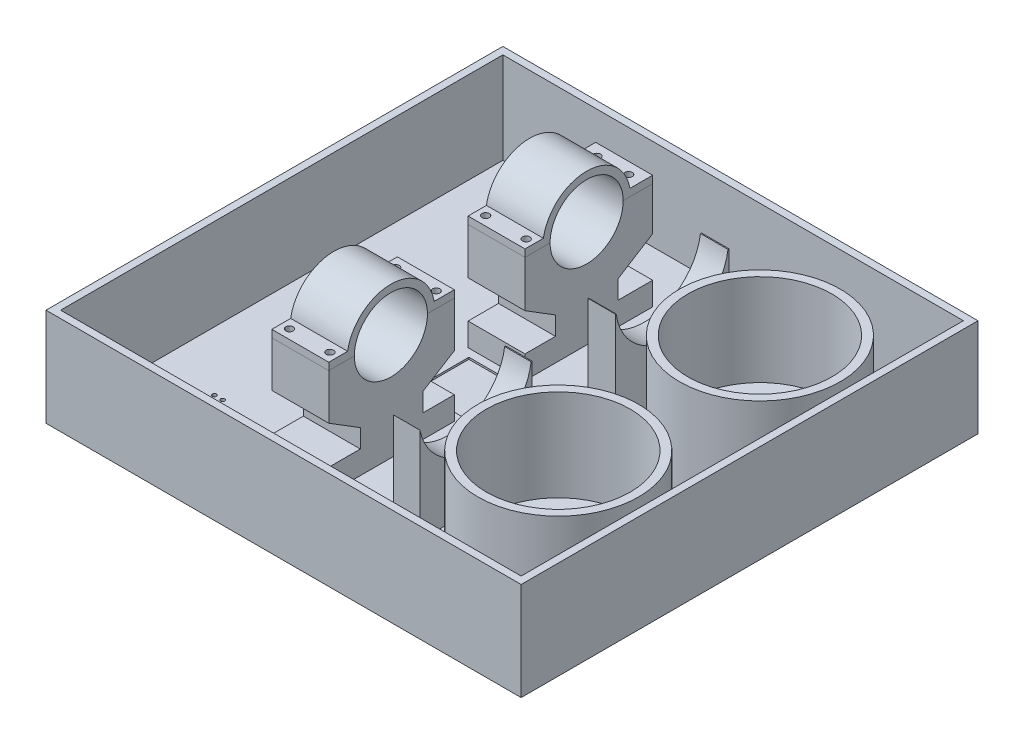
SolidWorks part; units mm, degrees
ref_plane "Front Plane" through (0, 0, 0) normal (0, 0, 1) x (1, 0, 0)
ref_plane "Top Plane" through (0, 0, 0) normal (0, 1, 0) x (1, 0, 0)
ref_plane "Right Plane" through (0, 0, 0) normal (1, 0, 0) x (0, 0, -1)
ref_plane "Plane1" through (0, -430, 0) normal (0, 1, 0) x (1, 0, 0)
sketch "Sketch2" plane through (0, -430, 0) normal (0, 1, 0) x (1, 0, 0)
  line L1 (-595.6003, 318.2592) -> (704.3997, 318.2592)
  line L2 (-595.6003, 318.2592) -> (-595.6003, -931.7408)
  line L3 (-595.6003, -931.7408) -> (704.3997, -931.7408)
  line L4 (704.3997, 318.2592) -> (704.3997, -931.7408)
  dimension "D1" = 1250
  dimension "D2" = 1300
extrude "Boss-Extrude1" add sketch "Sketch2" along normal blind 8 and the other way blind 10
sketch "Sketch3" plane through (0, -422, 0) normal (0, 1, 0) x (1, 0, 0)
  line L0 (-595.6003, -306.7408) -> (-355.8239, -306.7408) construction
  line L1 (-179.3433, 155.9673) -> (-23.5146, 155.9673)
  line L2 (-179.3433, 155.9673) -> (-179.3433, -193.2391)
  line L3 (-179.3433, -193.2391) -> (-23.5146, -193.2391)
  line L4 (-23.5146, 155.9673) -> (-23.5146, -193.2391)
  line L5 (-595.6003, 318.2592) -> (-595.6003, -931.7408) construction
  line L7 (-179.3433, -386.6168) -> (-23.5146, -386.6168)
  line L8 (-179.3433, -386.6168) -> (-179.3433, -730.1907)
  line L9 (-179.3433, -730.1907) -> (-23.5146, -730.1907)
  line L10 (-23.5146, -386.6168) -> (-23.5146, -730.1907)
extrude "Boss-Extrude2" add sketch "Sketch3" along normal blind 500 contours L10 L7 L8 L9 | L4 L1 L2 L3 region at (-101.429, -422, 18.6359) region at (-101.429, -422, 558.4038)
sketch "Sketch5" plane through (-23.5146, 0, 0) normal (1, 0, 0) x (0, 0, -1)
  line L0 (-730.1907, 78) -> (-730.1907, -422) construction
  line L1 (-730.1907, -150.0418) -> (-678.5462, -150.0418)
  line L2 (-730.1907, -110.0418) -> (-678.5462, -110.0418)
  line L3 (-730.1907, -110.0418) -> (-730.1907, -150.0418)
  line L4 (155.9673, 78) -> (155.9673, -422) construction
  line L5 (155.9673, -110.0418) -> (155.9673, -150.0418)
  line L6 (-386.6168, 78) -> (-386.6168, -422) construction
  line L7 (-386.6168, -110.0418) -> (-386.6168, -150.0418)
  line L8 (-193.2391, 78) -> (-193.2391, -422) construction
  line L9 (-193.2391, -110.0418) -> (-193.2391, -150.0418)
  line L10 (-193.2391, -110.0418) -> (-142.965, -110.0418)
  line L11 (-193.2391, -150.0418) -> (-142.965, -150.0418)
  line L12 (-441.8729, -110.0418) -> (-386.6168, -110.0418)
  line L13 (-441.8729, -150.0418) -> (-386.6168, -150.0418)
  line L14 (93.7083, -110.0418) -> (155.9673, -110.0418)
  line L15 (93.7083, -150.0418) -> (155.9673, -150.0418)
  line L16 (-193.2391, -422) -> (155.9673, -422) construction
  line L17 (155.9673, -422) -> (155.9673, 78) construction
  line L18 (155.9673, 78) -> (-193.2391, 78) construction
  line L19 (-730.1907, -422) -> (-386.6168, -422) construction
  line L20 (-386.6168, -422) -> (-386.6168, 78) construction
  line L21 (-386.6168, 78) -> (-730.1907, 78) construction
  line L22 (-193.2391, -422) -> (155.9673, -422)
  line L23 (155.9673, -422) -> (155.9673, 78)
  line L24 (155.9673, 78) -> (-193.2391, 78)
  line L25 (-193.2391, 78) -> (-193.2391, -422)
  line L26 (-730.1907, -422) -> (-386.6168, -422)
  line L27 (-386.6168, -422) -> (-386.6168, 78)
  line L28 (-386.6168, 78) -> (-730.1907, 78)
  line L29 (-730.1907, 78) -> (-730.1907, -422)
  line L30 (-730.1907, -254.6021) -> (-643.8745, -308.2123)
  line L31 (-643.8745, -308.2123) -> (-643.8745, -358.8441)
  line L32 (-643.8745, -358.8441) -> (-730.1907, -358.8441)
  line L33 (-558.4038, 78) -> (-558.4038, 43.2322) construction
  line L35 (-472.933, -308.2123) -> (-472.933, -358.8441)
  line L36 (-472.933, -358.8441) -> (-386.6168, -358.8441)
  line L37 (-386.6168, -254.6021) -> (-472.933, -308.2123)
  line L38 (-109.9414, -358.8441) -> (-193.2391, -358.8441)
  line L39 (-193.2391, -256.4769) -> (-109.9414, -308.2123)
  line L40 (-109.9414, -308.2123) -> (-109.9414, -358.8441)
  line L41 (61, -308.2123) -> (61, -358.8441)
  line L42 (61, -358.8441) -> (155.9673, -358.8441)
  line L43 (155.9673, -248.7059) -> (61, -308.2123)
  ellipse E13 centre (-560.2096, -130.0418) end of major axis (-660.2248, -130.0418) minor radius 100
  ellipse E14 centre (-24.6284, -130.0418) end of major axis (-124.6436, -130.0418) minor radius 100
  spline S1 degree 3 poles (-441.8729, -110.0418) (-442.0644, -108.909) (-442.9789, -103.936) (-444.2079, -99.017) (-445.9206, -93.3645) (-446.5404, -91.4865) (-447.8749, -87.7564) (-448.5856, -85.9156) (-450.8452, -80.4641) (-454.1975, -73.3846) (-458.2154, -66.6762) (-461.4808, -61.7853) (-462.6113, -60.1785) (-464.3712, -57.8039) (-464.9685, -57.0184) (-466.1848, -55.4593) (-466.8045, -54.6847) (-469.9429, -50.8607) (-472.5847, -47.9495) (-478.1222, -42.4136) (-481.0179, -39.789) (-487.0625, -34.8255) (-490.2113, -32.4865) (-494.3095, -29.746) (-495.1373, -29.207) (-496.8093, -28.1477) (-497.6536, -27.6274) (-500.197, -26.1029) (-501.9112, -25.1322) (-507.1089, -22.3549) (-514.1854, -19.0101) (-521.5498, -16.3704) (-527.1825, -14.6584) (-529.0783, -14.1325) (-532.9071, -13.1716) (-534.8448, -12.7359) (-540.6559, -11.5794) (-544.5398, -11.0048) (-552.3268, -10.2371) (-556.23, -10.044) (-564.0555, -10.0397) (-567.9778, -10.2283) (-573.8762, -10.806) (-575.8472, -11.0485) (-579.7511, -11.6268) (-581.6892, -11.9631) (-587.4623, -13.1108) (-595.0506, -15.0108) (-602.4234, -17.6413) (-607.8707, -19.8926) (-609.6727, -20.6895) (-612.3548, -21.956) (-613.2465, -22.3907) (-615.0144, -23.2796) (-615.891, -23.7341) (-620.2386, -26.0564) (-623.6024, -28.0729) (-630.1067, -32.4154) (-633.2474, -34.7415) (-639.3048, -39.7043) (-642.2215, -42.3411) (-645.7228, -45.8378) (-646.4158, -46.5472) (-647.7796, -47.9784) (-648.4513, -48.701) (-650.4365, -50.8898) (-651.7199, -52.377) (-655.4515, -56.9211) (-657.7816, -60.0605) (-662.1292, -66.5572) (-664.1467, -69.9145) (-666.9338, -75.1174) (-667.8229, -76.8795) (-669.5195, -80.4606) (-670.321, -82.2672) (-672.5828, -87.7222) (-673.9032, -91.4112) (-676.1765, -98.8913) (-677.1296, -102.6825) (-678.131, -107.6926) (-678.3472, -108.8648) (-678.5462, -110.0418) knots 0.026655 0.026655 0.026655 0.026655 0.03125 0.046875 0.046875 0.054687 0.054687 0.0625 0.0625 0.078125 0.09375 0.09375 0.101562 0.101562 0.105469 0.105469 0.109375 0.109375 0.125 0.125 0.140625 0.140625 0.15625 0.15625 0.160156 0.160156 0.164062 0.164062 0.171875 0.171875 0.1875 0.203125 0.203125 0.210937 0.210937 0.21875 0.21875 0.234375 0.234375 0.25 0.25 0.265625 0.265625 0.273437 0.273437 0.28125 0.28125 0.296875 0.3125 0.3125 0.320312 0.320312 0.324219 0.324219 0.328125 0.328125 0.34375 0.34375 0.359375 0.359375 0.375 0.375 0.378906 0.378906 0.382812 0.382812 0.390625 0.390625 0.40625 0.40625 0.421875 0.421875 0.429687 0.429687 0.4375 0.4375 0.453125 0.453125 0.46875 0.46875 0.473497 0.473497 0.473497 0.473497
  spline S3 degree 3 poles (-142.965, -150.0418) (-142.7787, -151.1439) (-142.5767, -152.2449) (-142.1676, -154.3113) (-141.964, -155.277) (-141.5322, -157.2067) (-141.3037, -158.172) (-140.5841, -161.0516) (-140.0588, -162.9518) (-138.3489, -168.5954) (-135.7124, -175.9679) (-132.3751, -183.0416) (-129.6064, -188.2334) (-128.6391, -189.9451) (-127.1205, -192.4838) (-126.603, -193.3252) (-125.5453, -194.9983) (-125.005, -195.8299) (-122.2616, -199.9404) (-119.9213, -203.0957) (-114.9585, -209.1484) (-112.3359, -212.0457) (-106.8088, -217.5826) (-103.9044, -220.2222) (-99.3303, -223.9829) (-97.7655, -225.206) (-94.5942, -227.5606) (-92.9853, -228.6946) (-88.0899, -231.9686) (-81.38, -235.9937) (-74.3097, -239.3479) (-68.8698, -241.6082) (-67.0336, -242.319) (-63.3145, -243.6537) (-61.4294, -244.2781) (-55.7659, -245.9999) (-51.9599, -246.9541) (-44.2887, -248.4853) (-40.4235, -249.0624) (-32.6339, -249.8385) (-28.7094, -250.0376) (-23.7656, -250.0428) (-22.7737, -250.0316) (-20.7956, -249.9847) (-19.8088, -249.9491) (-16.8551, -249.8061) (-14.8948, -249.6626) (-9.04, -249.0899) (-1.3032, -247.9478) (6.2959, -246.0565) (11.9426, -244.3518) (13.8161, -243.7358) (16.6128, -242.7387) (17.5427, -242.3941) (19.3876, -241.6844) (20.304, -241.3188) (24.8553, -239.4379) (28.3996, -237.7638) (35.2991, -234.0846) (38.6542, -232.0795) (45.1742, -227.7362) (48.339, -225.3981) (52.9385, -221.6324) (54.4359, -220.343) (57.3552, -217.7018) (58.778, -216.3493) (62.9375, -212.1973) (65.5654, -209.3036) (70.5333, -203.2664) (72.8732, -200.123) (75.614, -196.0342) (76.153, -195.2084) (77.2122, -193.5407) (77.7331, -192.6979) (79.2634, -190.1514) (80.2375, -188.4355) (83.0239, -183.234) (86.3779, -176.1557) (89.0232, -168.797) (90.739, -163.1719) (91.2661, -161.2791) (91.9886, -158.4129) (92.218, -157.453) (92.6539, -155.5241) (92.8605, -154.5541) (93.2906, -152.4047) (93.5084, -151.2242) (93.7083, -150.0418) knots 0.526804 0.526804 0.526804 0.526804 0.53125 0.53125 0.535156 0.535156 0.539062 0.539062 0.546875 0.546875 0.5625 0.578125 0.578125 0.585937 0.585937 0.589844 0.589844 0.59375 0.59375 0.609375 0.609375 0.625 0.625 0.640625 0.640625 0.648437 0.648437 0.65625 0.65625 0.671875 0.6875 0.6875 0.695312 0.695312 0.703125 0.703125 0.71875 0.71875 0.734375 0.734375 0.75 0.75 0.753906 0.753906 0.757812 0.757812 0.765625 0.765625 0.78125 0.796875 0.796875 0.804687 0.804687 0.808594 0.808594 0.8125 0.8125 0.828125 0.828125 0.84375 0.84375 0.859375 0.859375 0.867187 0.867187 0.875 0.875 0.890625 0.890625 0.90625 0.90625 0.910156 0.910156 0.914062 0.914062 0.921875 0.921875 0.9375 0.953125 0.953125 0.960937 0.960937 0.964844 0.964844 0.96875 0.96875 0.973493 0.973493 0.973493 0.973493
  spline S4 degree 3 poles (-678.5462, -150.0418) (-678.3599, -151.1439) (-678.1579, -152.2449) (-677.7488, -154.3113) (-677.5452, -155.277) (-677.1134, -157.2067) (-676.8849, -158.172) (-676.1653, -161.0516) (-675.64, -162.9518) (-673.9301, -168.5954) (-671.2936, -175.9679) (-667.9563, -183.0416) (-665.1876, -188.2334) (-664.2203, -189.9451) (-662.7017, -192.4838) (-662.1842, -193.3252) (-661.1265, -194.9983) (-660.5862, -195.8299) (-657.8428, -199.9404) (-655.5025, -203.0957) (-650.5397, -209.1484) (-647.9171, -212.0457) (-642.39, -217.5826) (-639.4856, -220.2222) (-634.9115, -223.9829) (-633.3467, -225.206) (-630.1754, -227.5606) (-628.5665, -228.6946) (-623.6711, -231.9686) (-616.9612, -235.9937) (-609.8909, -239.3479) (-604.451, -241.6082) (-602.6148, -242.319) (-598.8957, -243.6537) (-597.0106, -244.2781) (-591.3471, -245.9999) (-587.5411, -246.9541) (-579.8699, -248.4853) (-576.0047, -249.0624) (-568.2151, -249.8385) (-564.2906, -250.0376) (-559.3469, -250.0428) (-558.3549, -250.0316) (-556.3768, -249.9847) (-555.39, -249.9491) (-552.4363, -249.8061) (-550.476, -249.6626) (-544.6212, -249.0899) (-536.8844, -247.9478) (-529.2853, -246.0565) (-523.6386, -244.3518) (-521.7651, -243.7358) (-518.9684, -242.7387) (-518.0385, -242.3941) (-516.1936, -241.6844) (-515.2772, -241.3188) (-510.7259, -239.4379) (-507.1816, -237.7638) (-500.2821, -234.0846) (-496.927, -232.0795) (-490.4071, -227.7362) (-487.2422, -225.3981) (-482.6427, -221.6324) (-481.1453, -220.343) (-478.226, -217.7018) (-476.8032, -216.3493) (-472.6437, -212.1973) (-470.0158, -209.3036) (-465.0479, -203.2664) (-462.708, -200.123) (-459.9672, -196.0342) (-459.4283, -195.2084) (-458.369, -193.5407) (-457.8481, -192.6979) (-456.3178, -190.1514) (-455.3437, -188.4355) (-452.5573, -183.234) (-449.2033, -176.1557) (-446.558, -168.797) (-444.8422, -163.1719) (-444.3151, -161.2791) (-443.5926, -158.4129) (-443.3632, -157.453) (-442.9273, -155.5241) (-442.7207, -154.5541) (-442.2906, -152.4047) (-442.0728, -151.2242) (-441.8729, -150.0418) knots 0.526804 0.526804 0.526804 0.526804 0.53125 0.53125 0.535156 0.535156 0.539062 0.539062 0.546875 0.546875 0.5625 0.578125 0.578125 0.585937 0.585937 0.589844 0.589844 0.59375 0.59375 0.609375 0.609375 0.625 0.625 0.640625 0.640625 0.648437 0.648437 0.65625 0.65625 0.671875 0.6875 0.6875 0.695312 0.695312 0.703125 0.703125 0.71875 0.71875 0.734375 0.734375 0.75 0.75 0.753906 0.753906 0.757812 0.757812 0.765625 0.765625 0.78125 0.796875 0.796875 0.804687 0.804687 0.808594 0.808594 0.8125 0.8125 0.828125 0.828125 0.84375 0.84375 0.859375 0.859375 0.867187 0.867187 0.875 0.875 0.890625 0.890625 0.90625 0.90625 0.910156 0.910156 0.914062 0.914062 0.921875 0.921875 0.9375 0.953125 0.953125 0.960937 0.960937 0.964844 0.964844 0.96875 0.96875 0.973493 0.973493 0.973493 0.973493
  spline S5 degree 3 poles (93.7083, -110.0418) (93.5168, -108.909) (92.6023, -103.936) (91.3733, -99.017) (89.6606, -93.3645) (89.0409, -91.4865) (87.7063, -87.7564) (86.9956, -85.9156) (84.736, -80.4641) (81.3837, -73.3846) (77.3658, -66.6762) (74.1004, -61.7853) (72.9699, -60.1785) (71.21, -57.8039) (70.6127, -57.0184) (69.3964, -55.4593) (68.7767, -54.6847) (65.6383, -50.8607) (62.9965, -47.9495) (57.459, -42.4136) (54.5633, -39.789) (48.5187, -34.8255) (45.3699, -32.4865) (41.2717, -29.746) (40.4439, -29.207) (38.7719, -28.1477) (37.9276, -27.6274) (35.3843, -26.1029) (33.67, -25.1322) (28.4723, -22.3549) (21.3958, -19.0101) (14.0314, -16.3704) (8.3987, -14.6584) (6.5029, -14.1325) (2.6741, -13.1716) (0.7364, -12.7359) (-5.0746, -11.5794) (-8.9586, -11.0048) (-16.7456, -10.2371) (-20.6488, -10.044) (-28.4743, -10.0397) (-32.3966, -10.2283) (-38.295, -10.806) (-40.266, -11.0485) (-44.1699, -11.6268) (-46.108, -11.9631) (-51.8811, -13.1108) (-59.4694, -15.0108) (-66.8421, -17.6413) (-72.2895, -19.8926) (-74.0915, -20.6895) (-76.7736, -21.956) (-77.6653, -22.3907) (-79.4332, -23.2796) (-80.3098, -23.7341) (-84.6574, -26.0564) (-88.0212, -28.0729) (-94.5255, -32.4154) (-97.6662, -34.7415) (-103.7236, -39.7043) (-106.6403, -42.3411) (-110.1416, -45.8378) (-110.8346, -46.5472) (-112.1984, -47.9784) (-112.8701, -48.701) (-114.8553, -50.8898) (-116.1387, -52.377) (-119.8703, -56.9211) (-122.2004, -60.0605) (-126.548, -66.5572) (-128.5655, -69.9145) (-131.3526, -75.1174) (-132.2417, -76.8795) (-133.9383, -80.4606) (-134.7398, -82.2672) (-137.0016, -87.7222) (-138.3219, -91.4112) (-140.5953, -98.8913) (-141.5484, -102.6825) (-142.5498, -107.6926) (-142.766, -108.8648) (-142.965, -110.0418) knots 0.026655 0.026655 0.026655 0.026655 0.03125 0.046875 0.046875 0.054688 0.054688 0.0625 0.0625 0.078125 0.09375 0.09375 0.101563 0.101563 0.105469 0.105469 0.109375 0.109375 0.125 0.125 0.140625 0.140625 0.15625 0.15625 0.160156 0.160156 0.164063 0.164063 0.171875 0.171875 0.1875 0.203125 0.203125 0.210938 0.210938 0.21875 0.21875 0.234375 0.234375 0.25 0.25 0.265625 0.265625 0.273438 0.273438 0.28125 0.28125 0.296875 0.3125 0.3125 0.320313 0.320313 0.324219 0.324219 0.328125 0.328125 0.34375 0.34375 0.359375 0.359375 0.375 0.375 0.378906 0.378906 0.382812 0.382812 0.390625 0.390625 0.40625 0.40625 0.421875 0.421875 0.429687 0.429687 0.4375 0.4375 0.453125 0.453125 0.46875 0.46875 0.473497 0.473497 0.473497 0.473497
  line M10 (-386.6168, -422) -> (-386.6168, 78)
  line M11 (-386.6168, 78) -> (-730.1907, 78)
  line M12 (-730.1907, 78) -> (-730.1907, -422)
extrude "Cut-Extrude1" cut sketch "Sketch5" against normal up to surface (155.8286 mm away) contours S1 L12 L2 M10 M11 M12 | S5 L14 L23 L24 L25 L10 | E13 | E14 region at (-23.5146, 3.8699, 557.7123) region at (-23.5146, 3.4293, 16.3975) up to face at (-179.3433, -172, 18.6359)
extrude "Cut-Extrude2" cut sketch "Sketch5<3>" along direction (1, 0, 0) on the side against the normal up to vertex (155.8286 mm away) contours L32 L31 L30 L29 | L27 L37 L35 L36 | L40 L39 L25 L38 | L23 L43 L41 L42 region at (-23.5146, -318.5792, 692.0124) region at (-23.5146, -318.5792, 424.7951) region at (-23.5146, -316.8162, -114.3421) region at (-23.5146, -319.1365, 156.2847) up to point (-179.3433, -422, 730.1907)
sketch "Sketch5<3>" plane through (-23.5146, 0, 0) normal (1, 0, 0) x (0, 0, -1) same geometry as "Sketch5"
sketch "Sketch6" plane through (-23.5146, 0, 0) normal (1, 0, 0) x (0, 0, -1)
  line L0 (269.2759, -130.0418) -> (-802.0967, -130.0418)
split line "Split Line5"
sketch "Sketch7" plane through (0, -110.0418, 0) normal (0, 1, 0) x (1, 0, 0)
  circle A0 centre (-144.6532, 124.8378) radius 10
  circle A1 centre (-58.124, 124.8378) radius 10
  circle A2 centre (-156.2428, -168.102) radius 10
  circle A3 centre (-45.5571, -168.102) radius 10
  circle A4 centre (-156.2428, -414.2448) radius 10
  circle A5 centre (-45.5571, -414.2448) radius 10
  circle A6 centre (-156.2428, -704.9999) radius 10
  circle A7 centre (-45.5571, -704.9999) radius 10
  dimension "D1" = 20
extrude "Cut-Extrude3" cut sketch "Sketch7" against normal blind 60
sketch "Sketch8" plane through (0, -422, 0) normal (0, 1, 0) x (1, 0, 0)
  line L1 (139.0219, 126.9656) -> (214.4614, 126.9656)
  line L2 (139.0219, 126.9656) -> (139.0219, -183.2133)
  line L3 (139.0219, -183.2133) -> (214.4614, -183.2133)
  line L4 (214.4614, 126.9656) -> (214.4614, -183.2133)
  line L5 (139.0219, -408.6156) -> (211.5142, -408.6156)
  line L6 (139.0219, -408.6156) -> (139.0219, -715.7426)
  line L7 (139.0219, -715.7426) -> (211.5142, -715.7426)
  line L8 (211.5142, -408.6156) -> (211.5142, -715.7426)
extrude "Boss-Extrude4" add sketch "Sketch8" along normal blind 271
ref_plane "Plane2" through (271.5142, 0, 0) normal (1, 0, 0) x (0, 0, -1)
sketch "Sketch12" plane through (271.5142, 0, 0) normal (1, 0, 0) x (0, 0, -1)
  circle A0 centre (-564.4105, -130.0418) radius 154.4075
  circle A1 centre (-28.8293, -130.0418) radius 154.4781
extrude "Cut-Extrude9" cut sketch "Sketch12" against normal up to surface (132.4923 mm away) up to face at (139.0219, -286.5, 28.1238)
sketch "Sketch13" plane through (0, -422, 0) normal (0, 1, 0) x (1, 0, 0)
  circle A1 centre (458.9441, -584.6921) radius 196.8995
  circle A2 centre (461.8219, -35.9015) radius 219.7742
  circle A3 centre (458.9441, -584.6921) radius 219.7742
  ellipse E1 centre (461.8219, -35.9015) end of major axis (376.6695, -213.4359) minor radius 196.889
extrude "Boss-Extrude5" add sketch "Sketch13" along normal blind 271
extrude "Boss-Extrude6" add sketch "Sketch13<3>" along normal blind 20 contours A1 | E1 region at (458.9441, -422, 584.6921) region at (461.8219, -422, 35.9015)
sketch "Sketch13<3>" plane through (0, -422, 0) normal (0, 1, 0) x (1, 0, 0) same geometry as "Sketch13"
sketch "Sketch14" plane through (0, -422, 0) normal (0, 1, 0) x (1, 0, 0)
  line L0 (-595.6003, -931.7408) -> (704.3997, -931.7408) construction
  line L1 (-155.6003, -214.7008) -> (294.3997, -214.7008)
  line L2 (-155.6003, -214.7008) -> (-155.6003, -364.7008)
  line L3 (-155.6003, -364.7008) -> (294.3997, -364.7008)
  line L4 (294.3997, -214.7008) -> (294.3997, -364.7008)
  line L5 (-595.6003, 318.2592) -> (-595.6003, -931.7408) construction
  dimension "D1" = 150
  dimension "D2" = 450
  dimension "D3" = 567.04
  dimension "D4" = 440
extrude "Cut-Extrude10" cut sketch "Sketch14" against normal blind 5
sketch "Sketch15" plane through (0, -422, 0) normal (0, 1, 0) x (1, 0, 0)
  line L0 (-413.6003, 178.2592) -> (-391.1003, 178.2592) construction
  line L1 (-413.6003, 61.2692) -> (-391.1003, 61.2692) construction
  line L2 (-413.6003, -652.8008) -> (-413.6003, -769.7908) construction
  line L3 (-391.1003, -652.8008) -> (-391.1003, -769.7908) construction
  line L4 (-595.6003, 318.2592) -> (-595.6003, -931.7408) construction
  line L5 (704.3997, 318.2592) -> (-595.6003, 318.2592) construction
  line L6 (-595.6003, -931.7408) -> (704.3997, -931.7408) construction
  line L7 (-413.6003, 178.2592) -> (-413.6003, 61.2692) construction
  line L8 (-391.1003, 178.2592) -> (-391.1003, 61.2692) construction
  circle A0 centre (-413.6003, 178.2592) radius 5.57
  circle A1 centre (-391.1003, 178.2592) radius 5.57
  circle A2 centre (-413.6003, 61.2692) radius 5.57
  circle A3 centre (-391.1003, 61.2692) radius 5.57
  circle A4 centre (-413.6003, -769.7908) radius 5.57
  circle A5 centre (-413.6003, -652.8008) radius 5.57
  circle A6 centre (-391.1003, -652.8008) radius 5.57
  circle A7 centre (-391.1003, -769.7908) radius 5.57
  dimension "D1" = 11.14
  dimension "D2" = 116.99
  dimension "D3" = 116.99
  dimension "D4" = 116.99
  dimension "D6" = 182
  dimension "D7" = 182
  dimension "D8" = 22.5
  dimension "D9" = 22.5
  dimension "D10" = 140
  dimension "D11" = 161.95
extrude "Cut-Extrude11" cut sketch "Sketch15" against normal blind 10
sketch "Sketch16" plane through (0, -422, 0) normal (0, 1, 0) x (1, 0, 0)
  line L1 (-575.6003, 298.2592) -> (704.3997, 298.2592)
  line L2 (-575.6003, 298.2592) -> (-575.6003, -911.7408)
  line L3 (-575.6003, -911.7408) -> (704.3997, -911.7408)
  line L4 (-595.6003, 318.2592) -> (-595.6003, -931.7408)
  line L5 (-595.6003, -931.7408) -> (704.3997, -931.7408)
  line L6 (704.3997, -931.7408) -> (704.3997, 318.2592)
  line L7 (704.3997, 318.2592) -> (-595.6003, 318.2592)
  line L8 (-595.6003, 318.2592) -> (-595.6003, -931.7408)
  line L9 (-595.6003, -931.7408) -> (704.3997, -931.7408)
  line L10 (704.3997, -931.7408) -> (704.3997, 318.2592)
  line L11 (704.3997, 318.2592) -> (-595.6003, 318.2592)
  line M30 (-595.6003, 318.2592) -> (-595.6003, -931.7408)
  line M31 (-595.6003, -931.7408) -> (704.3997, -931.7408)
  line M32 (704.3997, -931.7408) -> (704.3997, 318.2592)
  line M33 (704.3997, 318.2592) -> (-595.6003, 318.2592)
  dimension "D2" = 20
  dimension "D3" = 20
  dimension "D4" = 20
  dimension "D1" = 0
sketch "Sketch17" plane through (0, -422, 0) normal (0, 1, 0) x (1, 0, 0)
  line L0 (704.3997, -931.7408) -> (704.3997, 318.2592) construction
  line L1 (704.3997, -931.7408) -> (704.3997, 318.2592)
extrude "Boss-Extrude7" add sketch "Sketch16" along normal blind 250 contours L3 L2 L1 M32 M33 M30 M31 region at (-593.635, -422, 306.7408)
extrude "Extrude-Thin1" add sketch "Sketch17" along normal blind 250 thin thin type one direction reverse wall 20
